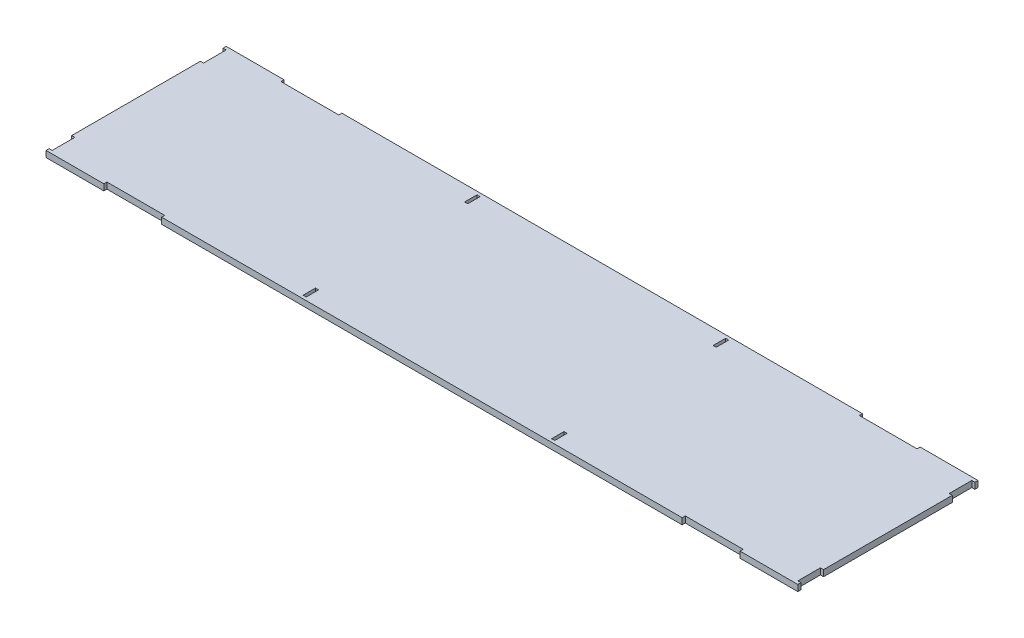
SolidWorks part; units mm, degrees
ref_plane "Front Plane" through (0, 0, 0) normal (0, 0, 1) x (1, 0, 0)
ref_plane "Top Plane" through (0, 0, 0) normal (0, 1, 0) x (1, 0, 0)
ref_plane "Right Plane" through (0, 0, 0) normal (1, 0, 0) x (0, 0, -1)
sketch "Sketch1" plane through (0, 0, 0) normal (0, 1, 0) x (1, 0, 0)
  line L0 (0, 88.9) -> (0, -88.9) construction
  line L1 (-381, 88.9) -> (381, 88.9)
  line L2 (-381, 88.9) -> (-381, -88.9)
  line L3 (-381, -88.9) -> (381, -88.9)
  line L4 (381, 88.9) -> (381, -88.9)
  line L5 (-381, 39.4607) -> (-381, 65.7679)
  line L6 (-381, 65.7679) -> (-384.175, 65.7679)
  line L7 (-381, 65.7679) -> (-381, 92.075)
  line L8 (-381, 92.075) -> (-384.175, 92.075)
  line L9 (-384.175, 65.7679) -> (-384.175, 92.075)
  line L14 (-325.0712, -88.9) -> (-384.175, -88.9)
  line L15 (-325.0712, -88.9) -> (-325.0712, -92.075)
  line L16 (-325.0712, -92.075) -> (-384.175, -92.075)
  line L17 (-384.175, -88.9) -> (-384.175, -92.075)
  line L18 (381, 65.7679) -> (384.175, 65.7679)
  line L19 (381, 65.7679) -> (381, 92.075)
  line L20 (381, 92.075) -> (384.175, 92.075)
  line L21 (384.175, 65.7679) -> (384.175, 92.075)
  line L22 (-325.0712, 88.9) -> (-384.175, 88.9)
  line L23 (-325.0712, 88.9) -> (-325.0712, 92.075)
  line L24 (-325.0712, 92.075) -> (-384.175, 92.075)
  line L25 (-384.175, 88.9) -> (-384.175, 92.075)
  line L26 (-381, 39.4607) -> (-384.175, 39.4607)
  line L27 (-384.175, 39.4607) -> (-384.175, 65.7679)
  line L28 (-381, 65.7679) -> (-384.175, 65.7679)
  line L29 (381, 39.4607) -> (381, 65.7679)
  line L30 (381, 39.4607) -> (384.175, 39.4607)
  line L31 (384.175, 39.4607) -> (384.175, 65.7679)
  line L32 (381, 65.7679) -> (384.175, 65.7679)
  line L33 (-381, 13.1536) -> (-381, 39.4607)
  line L34 (-381, 13.1536) -> (-384.175, 13.1536)
  line L35 (-384.175, 13.1536) -> (-384.175, 39.4607)
  line L36 (-381, 39.4607) -> (-384.175, 39.4607)
  line L37 (381, 13.1536) -> (381, 39.4607)
  line L38 (381, 13.1536) -> (384.175, 13.1536)
  line L39 (384.175, 13.1536) -> (384.175, 39.4607)
  line L40 (381, 39.4607) -> (384.175, 39.4607)
  line L41 (-381, -13.1536) -> (-381, 13.1536)
  line L42 (-381, -13.1536) -> (-384.175, -13.1536)
  line L43 (-384.175, -13.1536) -> (-384.175, 13.1536)
  line L44 (-381, 13.1536) -> (-384.175, 13.1536)
  line L45 (381, -13.1536) -> (381, 13.1536)
  line L46 (381, -13.1536) -> (384.175, -13.1536)
  line L47 (384.175, -13.1536) -> (384.175, 13.1536)
  line L48 (381, 13.1536) -> (384.175, 13.1536)
  line L49 (-381, -39.4607) -> (-381, -13.1536)
  line L50 (-381, -39.4607) -> (-384.175, -39.4607)
  line L51 (-384.175, -39.4607) -> (-384.175, -13.1536)
  line L52 (-381, -13.1536) -> (-384.175, -13.1536)
  line L53 (381, -39.4607) -> (381, -13.1536)
  line L54 (381, -39.4607) -> (384.175, -39.4607)
  line L55 (384.175, -39.4607) -> (384.175, -13.1536)
  line L56 (381, -13.1536) -> (384.175, -13.1536)
  line L57 (-381, -65.7679) -> (-381, -39.4607)
  line L58 (-381, -65.7679) -> (-384.175, -65.7679)
  line L59 (-384.175, -65.7679) -> (-384.175, -39.4607)
  line L60 (-381, -39.4607) -> (-384.175, -39.4607)
  line L61 (381, -65.7679) -> (381, -39.4607)
  line L62 (381, -65.7679) -> (384.175, -65.7679)
  line L63 (384.175, -65.7679) -> (384.175, -39.4607)
  line L64 (381, -39.4607) -> (384.175, -39.4607)
  line L65 (-381, -92.075) -> (-381, -65.7679)
  line L66 (-381, -92.075) -> (-384.175, -92.075)
  line L67 (-384.175, -92.075) -> (-384.175, -65.7679)
  line L68 (-381, -65.7679) -> (-384.175, -65.7679)
  line L69 (381, -92.075) -> (381, -65.7679)
  line L70 (381, -92.075) -> (384.175, -92.075)
  line L71 (384.175, -92.075) -> (384.175, -65.7679)
  line L72 (381, -65.7679) -> (384.175, -65.7679)
  line L73 (-265.9673, -88.9) -> (-265.9673, -92.075)
  line L74 (-265.9673, -88.9) -> (-325.0712, -88.9)
  line L75 (-325.0712, -88.9) -> (-325.0712, -92.075)
  line L76 (-265.9673, -92.075) -> (-325.0712, -92.075)
  line L77 (-265.9673, 88.9) -> (-265.9673, 92.075)
  line L78 (-265.9673, 88.9) -> (-325.0712, 88.9)
  line L79 (-325.0712, 88.9) -> (-325.0712, 92.075)
  line L80 (-265.9673, 92.075) -> (-325.0712, 92.075)
  line L81 (-206.8635, -88.9) -> (-206.8635, -92.075)
  line L82 (-206.8635, -88.9) -> (-265.9673, -88.9)
  line L83 (-265.9673, -88.9) -> (-265.9673, -92.075)
  line L84 (-206.8635, -92.075) -> (-265.9673, -92.075)
  line L85 (-206.8635, 88.9) -> (-206.8635, 92.075)
  line L86 (-206.8635, 88.9) -> (-265.9673, 88.9)
  line L87 (-265.9673, 88.9) -> (-265.9673, 92.075)
  line L88 (-206.8635, 92.075) -> (-265.9673, 92.075)
  line L89 (-147.7596, -88.9) -> (-147.7596, -92.075)
  line L90 (-147.7596, -88.9) -> (-206.8635, -88.9)
  line L91 (-206.8635, -88.9) -> (-206.8635, -92.075)
  line L92 (-147.7596, -92.075) -> (-206.8635, -92.075)
  line L93 (-147.7596, 88.9) -> (-147.7596, 92.075)
  line L94 (-147.7596, 88.9) -> (-206.8635, 88.9)
  line L95 (-206.8635, 88.9) -> (-206.8635, 92.075)
  line L96 (-147.7596, 92.075) -> (-206.8635, 92.075)
  line L97 (-88.6558, -88.9) -> (-88.6558, -92.075)
  line L98 (-88.6558, -88.9) -> (-147.7596, -88.9)
  line L99 (-147.7596, -88.9) -> (-147.7596, -92.075)
  line L100 (-88.6558, -92.075) -> (-147.7596, -92.075)
  line L101 (-88.6558, 88.9) -> (-88.6558, 92.075)
  line L102 (-88.6558, 88.9) -> (-147.7596, 88.9)
  line L103 (-147.7596, 88.9) -> (-147.7596, 92.075)
  line L104 (-88.6558, 92.075) -> (-147.7596, 92.075)
  line L105 (-29.5519, -88.9) -> (-29.5519, -92.075)
  line L106 (-29.5519, -88.9) -> (-88.6558, -88.9)
  line L107 (-88.6558, -88.9) -> (-88.6558, -92.075)
  line L108 (-29.5519, -92.075) -> (-88.6558, -92.075)
  line L109 (-29.5519, 88.9) -> (-29.5519, 92.075)
  line L110 (-29.5519, 88.9) -> (-88.6558, 88.9)
  line L111 (-88.6558, 88.9) -> (-88.6558, 92.075)
  line L112 (-29.5519, 92.075) -> (-88.6558, 92.075)
  line L113 (29.5519, -88.9) -> (29.5519, -92.075)
  line L114 (29.5519, -88.9) -> (-29.5519, -88.9)
  line L115 (-29.5519, -88.9) -> (-29.5519, -92.075)
  line L116 (29.5519, -92.075) -> (-29.5519, -92.075)
  line L117 (29.5519, 88.9) -> (29.5519, 92.075)
  line L118 (29.5519, 88.9) -> (-29.5519, 88.9)
  line L119 (-29.5519, 88.9) -> (-29.5519, 92.075)
  line L120 (29.5519, 92.075) -> (-29.5519, 92.075)
  line L121 (88.6558, -88.9) -> (88.6558, -92.075)
  line L122 (88.6558, -88.9) -> (29.5519, -88.9)
  line L123 (29.5519, -88.9) -> (29.5519, -92.075)
  line L124 (88.6558, -92.075) -> (29.5519, -92.075)
  line L125 (88.6558, 88.9) -> (88.6558, 92.075)
  line L126 (88.6558, 88.9) -> (29.5519, 88.9)
  line L127 (29.5519, 88.9) -> (29.5519, 92.075)
  line L128 (88.6558, 92.075) -> (29.5519, 92.075)
  line L129 (147.7596, -88.9) -> (147.7596, -92.075)
  line L130 (147.7596, -88.9) -> (88.6558, -88.9)
  line L131 (88.6558, -88.9) -> (88.6558, -92.075)
  line L132 (147.7596, -92.075) -> (88.6558, -92.075)
  line L133 (147.7596, 88.9) -> (147.7596, 92.075)
  line L134 (147.7596, 88.9) -> (88.6558, 88.9)
  line L135 (88.6558, 88.9) -> (88.6558, 92.075)
  line L136 (147.7596, 92.075) -> (88.6558, 92.075)
  line L137 (206.8635, -88.9) -> (206.8635, -92.075)
  line L138 (206.8635, -88.9) -> (147.7596, -88.9)
  line L139 (147.7596, -88.9) -> (147.7596, -92.075)
  line L140 (206.8635, -92.075) -> (147.7596, -92.075)
  line L141 (206.8635, 88.9) -> (206.8635, 92.075)
  line L142 (206.8635, 88.9) -> (147.7596, 88.9)
  line L143 (147.7596, 88.9) -> (147.7596, 92.075)
  line L144 (206.8635, 92.075) -> (147.7596, 92.075)
  line L145 (265.9673, -88.9) -> (265.9673, -92.075)
  line L146 (265.9673, -88.9) -> (206.8635, -88.9)
  line L147 (206.8635, -88.9) -> (206.8635, -92.075)
  line L148 (265.9673, -92.075) -> (206.8635, -92.075)
  line L149 (265.9673, 88.9) -> (265.9673, 92.075)
  line L150 (265.9673, 88.9) -> (206.8635, 88.9)
  line L151 (206.8635, 88.9) -> (206.8635, 92.075)
  line L152 (265.9673, 92.075) -> (206.8635, 92.075)
  line L185 (325.0712, -88.9) -> (325.0712, -92.075)
  line L186 (325.0712, -88.9) -> (265.9673, -88.9)
  line L187 (265.9673, -88.9) -> (265.9673, -92.075)
  line L188 (325.0712, -92.075) -> (265.9673, -92.075)
  line L189 (325.0712, 88.9) -> (325.0712, 92.075)
  line L190 (325.0712, 88.9) -> (265.9673, 88.9)
  line L191 (265.9673, 88.9) -> (265.9673, 92.075)
  line L192 (325.0712, 92.075) -> (265.9673, 92.075)
  line L193 (384.175, -88.9) -> (384.175, -92.075)
  line L194 (384.175, -88.9) -> (325.0712, -88.9)
  line L195 (325.0712, -88.9) -> (325.0712, -92.075)
  line L196 (384.175, -92.075) -> (325.0712, -92.075)
  line L197 (384.175, 88.9) -> (384.175, 92.075)
  line L198 (384.175, 88.9) -> (325.0712, 88.9)
  line L199 (325.0712, 88.9) -> (325.0712, 92.075)
  line L200 (384.175, 92.075) -> (325.0712, 92.075)
  point P8 (0, 88.9)
  point P9 (0, 0)
  dimension "D1" = 762
  dimension "D2" = 177.8
  dimension "D3" = 184.15
  dimension "D5" = 768.35
  dimension "D6" = 26.3071
  dimension "D8" = 59.1038
  dimension "D4" = 7
  dimension "D7" = 13
extrude "Boss-Extrude1" add sketch "Sketch1" along normal blind 6.35 contours L0 L1 L2 L3 | L126 L0 L122 L3 L4 L1 | L65 L16 L15 L3 | L16 L65 L14 L17 | L84 L81 L3 L73 | L59 L58 L2 L50 | L100 L97 L3 L89 | L43 L42 L2 L34 | L27 L26 L2 L6 | L22 L7 L8 L9 | L23 L24 L7 L1 | L85 L88 L77 L1 | L101 L104 L93 L1 | L117 L120 L109 L1 | L133 L136 L125 L1 | L116 L113 L3 L105 | L132 L129 L3 L121 | L148 L145 L3 L137 | L149 L152 L141 L1 | L21 L20 L19 | L30 L31 L18 L4 | L46 L47 L38 L4 | L62 L63 L54 L4 | L71 L69 L70 | L193 L196 L195 L194 | L197 L200 L199 L198 region at (190.5, 0, 0) region at (-190.5, 0, 0) region at (0, 0, -90.4875) region at (0, 0, 90.4875) region at (-118.2077, 0, -90.4875) region at (118.2077, 0, -90.4875) region at (-118.2077, 0, 90.4875) region at (118.2077, 0, 90.4875) region at (-236.4154, 0, -90.4875) region at (236.4154, 0, -90.4875) region at (-236.4154, 0, 90.4875) region at (236.4154, 0, 90.4875) region at (-353.0356, 0, -90.4875) region at (-353.0356, 0, 90.4875) region at (-382.5875, 0, -90.4875) region at (382.5875, 0, -90.4875) region at (-382.5875, 0, 90.4875) region at (382.5875, 0, 90.4875) region at (-382.5875, 0, -52.6143) region at (382.5875, 0, -52.6143) region at (-382.5875, 0, 52.6143) region at (382.5875, 0, 52.6143) region at (-382.5875, 0, 0) region at (382.5875, 0, 0)
sketch "Sketch2" plane through (0, 6.35, 0) normal (0, 1, 0) x (1, 0, 0)
  line L0 (-125.4125, 0) -> (125.4125, 0) construction
  line L1 (-128.5875, 15.4404) -> (-125.4125, 15.4404) construction
  line L2 (-128.5875, 15.4404) -> (-128.5875, -15.4404) construction
  line L3 (-128.5875, -15.4404) -> (-125.4125, -15.4404) construction
  line L4 (-125.4125, 15.4404) -> (-125.4125, -15.4404) construction
  line L5 (125.4125, 14.3164) -> (128.5875, 14.3164) construction
  line L6 (125.4125, 14.3164) -> (125.4125, -14.3164) construction
  line L7 (125.4125, -14.3164) -> (128.5875, -14.3164) construction
  line L8 (128.5875, 14.3164) -> (128.5875, -14.3164) construction
  line L9 (-129.3813, 24.6215) -> (-124.6188, 24.6215) construction
  line L10 (-127, 24.6215) -> (-127, 15.4404) construction
  line L12 (-124.6188, 76.2) -> (-121.4438, 76.2)
  line L13 (-124.6188, 76.2) -> (-124.6188, 88.9)
  line L14 (-124.6188, 88.9) -> (-121.4438, 88.9)
  line L15 (-121.4438, 76.2) -> (-121.4438, 88.9)
  line L16 (-124.6188, 24.6215) -> (-124.6188, 76.2) construction
  line L18 (-121.4438, -88.9) -> (-124.6188, -88.9)
  line L19 (-121.4438, -88.9) -> (-121.4438, -76.2)
  line L20 (-121.4438, -76.2) -> (-124.6188, -76.2)
  line L21 (-124.6188, -88.9) -> (-124.6188, -76.2)
  line L31 (-206.8635, 88.9) -> (-147.7596, 88.9) construction
  line L32 (-206.8635, -88.9) -> (-147.7596, -88.9) construction
  line L33 (129.3813, 76.2) -> (129.3812, 88.9)
  line L34 (129.3813, 76.2) -> (132.5562, 76.2)
  line L35 (132.5562, 76.2) -> (132.5562, 88.9)
  line L36 (129.3812, 88.9) -> (132.5562, 88.9)
  line L37 (132.5562, -88.9) -> (132.5562, -76.2)
  line L38 (132.5562, -88.9) -> (129.3812, -88.9)
  line L39 (129.3812, -88.9) -> (129.3812, -76.2)
  line L40 (132.5562, -76.2) -> (129.3812, -76.2)
  line L41 (124.6188, 24.6215) -> (129.3813, 24.6215) construction
  line L42 (127, 24.6215) -> (127, 14.3164) construction
  line L43 (129.3813, 24.6215) -> (129.3813, 76.2) construction
  point P10 (0, 0)
  point P43 (127, 14.3164)
  dimension "D1" = 3.175
  dimension "D2" = 4.7625
  dimension "D4" = 3.175
  dimension "D5" = 12.7
  dimension "D3" = 254
  dimension "D6" = 2
extrude "Cut-Extrude1" cut sketch "Sketch2" against normal through all
sketch "Sketch3" plane through (0, 6.35, 0) normal (0, 1, 0) x (1, 0, 0)
  line L1 (-206.8635, -92.075) -> (-147.7596, -92.075)
  line L2 (-206.8635, -92.075) -> (-206.8635, -88.9)
  line L3 (-206.8635, -88.9) -> (-147.7596, -88.9)
  line L4 (-147.7596, -92.075) -> (-147.7596, -88.9)
  line L5 (-88.6558, -92.075) -> (-29.5519, -92.075)
  line L6 (-88.6558, -92.075) -> (-88.6558, -88.9)
  line L7 (-88.6558, -88.9) -> (-29.5519, -88.9)
  line L8 (-29.5519, -92.075) -> (-29.5519, -88.9)
  line L9 (29.5519, -92.075) -> (88.6558, -92.075)
  line L10 (29.5519, -92.075) -> (29.5519, -88.9)
  line L11 (29.5519, -88.9) -> (88.6558, -88.9)
  line L12 (88.6558, -92.075) -> (88.6558, -88.9)
  line L13 (147.7596, -92.075) -> (206.8635, -92.075)
  line L14 (147.7596, -92.075) -> (147.7596, -88.9)
  line L15 (147.7596, -88.9) -> (206.8635, -88.9)
  line L16 (206.8635, -92.075) -> (206.8635, -88.9)
  line L17 (384.175, -39.4607) -> (381, -39.4607)
  line L18 (384.175, -39.4607) -> (384.175, -13.1536)
  line L19 (384.175, -13.1536) -> (381, -13.1536)
  line L20 (381, -39.4607) -> (381, -13.1536)
  line L21 (384.175, 13.1536) -> (381, 13.1536)
  line L22 (384.175, 13.1536) -> (384.175, 39.4607)
  line L23 (384.175, 39.4607) -> (381, 39.4607)
  line L24 (381, 13.1536) -> (381, 39.4607)
  line L25 (-384.175, -13.1536) -> (-381, -13.1536)
  line L26 (-384.175, -13.1536) -> (-384.175, -39.4607)
  line L27 (-384.175, -39.4607) -> (-381, -39.4607)
  line L28 (-381, -13.1536) -> (-381, -39.4607)
  line L29 (-384.175, 39.4607) -> (-381, 39.4607)
  line L30 (-384.175, 39.4607) -> (-384.175, 13.1536)
  line L31 (-384.175, 13.1536) -> (-381, 13.1536)
  line L32 (-381, 39.4607) -> (-381, 13.1536)
  line L33 (-206.8635, 88.9) -> (-147.7596, 88.9)
  line L34 (-206.8635, 88.9) -> (-206.8635, 92.075)
  line L35 (-206.8635, 92.075) -> (-147.7596, 92.075)
  line L36 (-147.7596, 88.9) -> (-147.7596, 92.075)
  line L37 (-88.6558, 88.9) -> (-29.5519, 88.9)
  line L38 (-88.6558, 88.9) -> (-88.6558, 92.075)
  line L39 (-88.6558, 92.075) -> (-29.5519, 92.075)
  line L40 (-29.5519, 88.9) -> (-29.5519, 92.075)
  line L41 (29.5519, 88.9) -> (88.6558, 88.9)
  line L42 (29.5519, 88.9) -> (29.5519, 92.075)
  line L43 (29.5519, 92.075) -> (88.6558, 92.075)
  line L44 (88.6558, 88.9) -> (88.6558, 92.075)
  line L45 (147.7596, 88.9) -> (206.8635, 88.9)
  line L46 (147.7596, 88.9) -> (147.7596, 92.075)
  line L47 (147.7596, 92.075) -> (206.8635, 92.075)
  line L48 (206.8635, 88.9) -> (206.8635, 92.075)
extrude "Boss-Extrude2" add sketch "Sketch3" against normal up to surface (6.35 mm away) up to face at (130.9687, 0, -82.55)
equation "\"Height\"= 12in"
equation "\"Depth\"= 7in"
equation "\"WallThickness\"= 0.125in"
equation "\"FloorThickness\"= 0.25in"
equation "\"D1@Sketch1\"=\"Width\""
equation "\"D2@Sketch1\"=\"Depth\""
equation "\"D3@Sketch1\"=\"D2@Sketch1\"+2*\"WallThickness\""
equation "\"D5@Sketch1\"=\"D1@Sketch1\"+2*\"WallThickness\""
equation "\"D6@Sketch1\"=\"D3@Sketch1\"/\"D4@Sketch1\""
equation "\"D8@Sketch1\"=\"D5@Sketch1\"/\"D7@Sketch1\""
equation "\"D1@Boss-Extrude1\"=\"FloorThickness\""
equation "\"D1@Sketch2\"=\"WallThickness\""
equation "\"D2@Sketch2\"=\"WallThickness\"+(1/16in)"
equation "\"D4@Sketch2\"=\"WallThickness\""
equation "\"Width\" = 30in"
